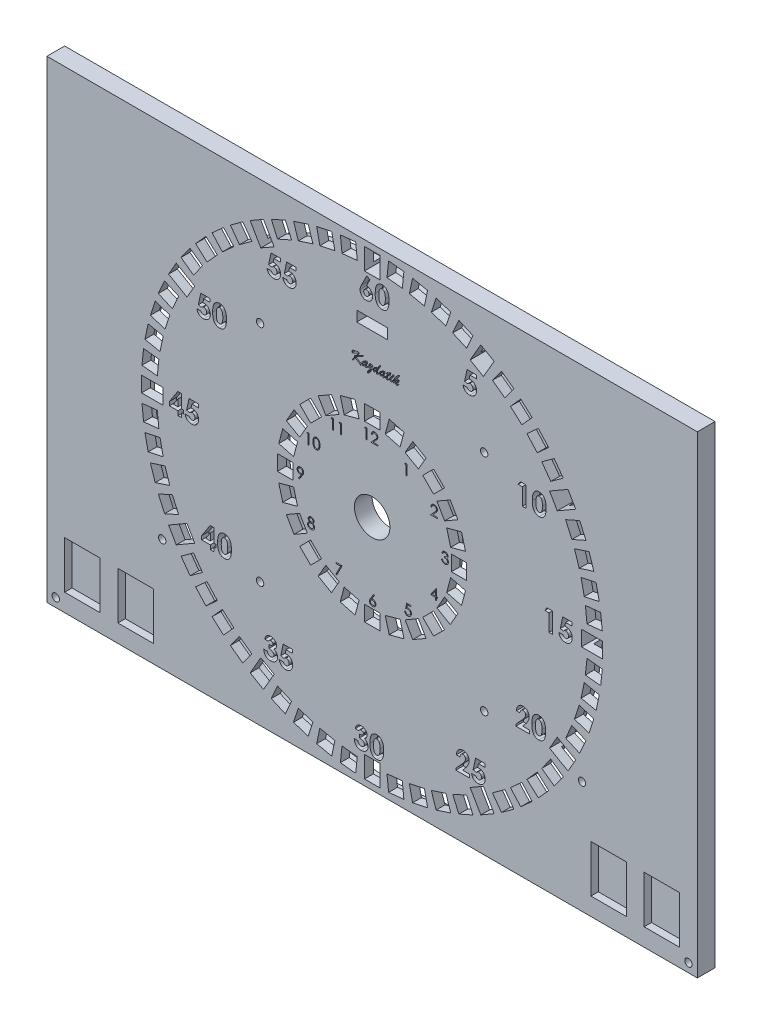
SolidWorks part; units mm, degrees
ref_plane "Front Plane" through (0, 0, 0) normal (0, 0, 1) x (1, 0, 0)
ref_plane "Top Plane" through (0, 0, 0) normal (0, 1, 0) x (1, 0, 0)
ref_plane "Right Plane" through (0, 0, 0) normal (1, 0, 0) x (0, 0, -1)
sketch "Sketch1" plane through (0, 0, 0) normal (0, 0, 1) x (1, 0, 0)
  line L1 (0, 0) -> (220, 0)
  line L2 (0, 0) -> (0, 160)
  line L3 (0, 160) -> (220, 160)
  line L4 (220, 0) -> (220, 160)
  line L5 (112.6, 158) -> (107.4, 158)
  line L6 (107.4, 158) -> (107.4, 152.8)
  line L7 (107.4, 152.8) -> (112.6, 152.8)
  line L8 (112.6, 158) -> (112.6, 152.8)
  line L9 (115.5675, 157.8445) -> (115.0239, 152.673)
  line L16 (120.739, 157.3009) -> (115.5675, 157.8445)
  line L19 (120.739, 157.3009) -> (120.1954, 152.1294)
  line L20 (115.0239, 152.673) -> (120.1954, 152.1294)
  line L27 (123.6739, 156.8361) -> (122.5928, 151.7497)
  line L30 (128.7603, 155.7549) -> (123.6739, 156.8361)
  line L31 (128.7603, 155.7549) -> (127.6792, 150.6686)
  line L37 (122.5928, 151.7497) -> (127.6792, 150.6686)
  line L42 (131.6306, 154.9859) -> (130.0237, 150.0404)
  line L46 (136.5761, 153.379) -> (131.6306, 154.9859)
  line L48 (136.5761, 153.379) -> (134.9692, 148.4335)
  line L55 (130.0237, 150.0404) -> (134.9692, 148.4335)
  line L58 (139.3502, 152.3141) -> (137.2352, 147.5636)
  line L64 (144.1007, 150.199) -> (139.3502, 152.3141)
  line L68 (144.1007, 150.199) -> (141.9856, 145.4486)
  line L72 (104.8, 138.0481) -> (115.2, 138.0481)
  line L73 (115.2, 138.0481) -> (115.2, 134.5481)
  line L74 (115.2, 134.5481) -> (104.8, 134.5481)
  line L75 (104.8, 138.0481) -> (104.8, 134.5481)
  line L76 (137.2352, 147.5636) -> (141.9856, 145.4486)
  line L81 (146.7483, 148.85) -> (144.1483, 144.3466)
  line L86 (151.2517, 146.25) -> (146.7483, 148.85)
  line L95 (151.2517, 146.25) -> (148.6517, 141.7466)
  line L534 (144.1483, 144.3466) -> (148.6517, 141.7466)
  line L535 (153.7438, 144.6316) -> (150.6873, 140.4247)
  line L536 (157.9507, 141.5751) -> (153.7438, 144.6316)
  line L537 (157.9507, 141.5751) -> (154.8942, 137.3682)
  line L538 (150.6873, 140.4247) -> (154.8942, 137.3682)
  line L539 (160.26, 139.705) -> (156.7805, 135.8407)
  line L540 (164.1244, 136.2256) -> (160.26, 139.705)
  line L541 (164.1244, 136.2256) -> (160.6449, 132.3612)
  line L542 (156.7805, 135.8407) -> (160.6449, 132.3612)
  line L543 (166.2256, 134.1244) -> (162.3612, 130.6449)
  line L544 (169.705, 130.26) -> (166.2256, 134.1244)
  line L545 (169.705, 130.26) -> (165.8407, 126.7805)
  line L546 (162.3612, 130.6449) -> (165.8407, 126.7805)
  line L547 (171.5751, 127.9507) -> (167.3682, 124.8942)
  line L548 (174.6316, 123.7438) -> (171.5751, 127.9507)
  line L549 (174.6316, 123.7438) -> (170.4247, 120.6873)
  line L550 (167.3682, 124.8942) -> (170.4247, 120.6873)
  line L551 (176.25, 121.2517) -> (171.7466, 118.6517)
  line L552 (178.85, 116.7483) -> (176.25, 121.2517)
  line L553 (178.85, 116.7483) -> (174.3466, 114.1483)
  line L554 (171.7466, 118.6517) -> (174.3466, 114.1483)
  line L555 (180.199, 114.1007) -> (175.4486, 111.9856)
  line L556 (182.3141, 109.3502) -> (180.199, 114.1007)
  line L557 (182.3141, 109.3502) -> (177.5636, 107.2352)
  line L558 (175.4486, 111.9856) -> (177.5636, 107.2352)
  line L559 (183.379, 106.5761) -> (178.4335, 104.9692)
  line L560 (184.9859, 101.6306) -> (183.379, 106.5761)
  line L561 (184.9859, 101.6306) -> (180.0404, 100.0237)
  line L562 (178.4335, 104.9692) -> (180.0404, 100.0237)
  line L563 (185.7549, 98.7603) -> (180.6686, 97.6792)
  line L564 (186.8361, 93.6739) -> (185.7549, 98.7603)
  line L565 (186.8361, 93.6739) -> (181.7497, 92.5928)
  line L566 (180.6686, 97.6792) -> (181.7497, 92.5928)
  line L567 (187.3009, 90.739) -> (182.1294, 90.1954)
  line L568 (187.8445, 85.5675) -> (187.3009, 90.739)
  line L569 (187.8445, 85.5675) -> (182.673, 85.0239)
  line L570 (182.1294, 90.1954) -> (182.673, 85.0239)
  line L571 (188, 82.6) -> (182.8, 82.6)
  line L572 (188, 77.4) -> (188, 82.6)
  line L573 (188, 77.4) -> (182.8, 77.4)
  line L574 (182.8, 82.6) -> (182.8, 77.4)
  line L575 (187.8445, 74.4325) -> (182.673, 74.9761)
  line L576 (187.3009, 69.261) -> (187.8445, 74.4325)
  line L577 (187.3009, 69.261) -> (182.1294, 69.8046)
  line L578 (182.673, 74.9761) -> (182.1294, 69.8046)
  line L579 (186.8361, 66.3261) -> (181.7497, 67.4072)
  line L580 (185.7549, 61.2397) -> (186.8361, 66.3261)
  line L581 (185.7549, 61.2397) -> (180.6686, 62.3208)
  line L582 (181.7497, 67.4072) -> (180.6686, 62.3208)
  line L583 (184.9859, 58.3694) -> (180.0404, 59.9763)
  line L584 (183.379, 53.4239) -> (184.9859, 58.3694)
  line L585 (183.379, 53.4239) -> (178.4335, 55.0308)
  line L586 (180.0404, 59.9763) -> (178.4335, 55.0308)
  line L587 (182.3141, 50.6498) -> (177.5636, 52.7648)
  line L588 (180.199, 45.8993) -> (182.3141, 50.6498)
  line L589 (180.199, 45.8993) -> (175.4486, 48.0144)
  line L590 (177.5636, 52.7648) -> (175.4486, 48.0144)
  line L591 (178.85, 43.2517) -> (174.3466, 45.8517)
  line L592 (176.25, 38.7483) -> (178.85, 43.2517)
  line L593 (176.25, 38.7483) -> (171.7466, 41.3483)
  line L594 (174.3466, 45.8517) -> (171.7466, 41.3483)
  line L595 (174.6316, 36.2562) -> (170.4247, 39.3127)
  line L596 (171.5751, 32.0493) -> (174.6316, 36.2562)
  line L597 (171.5751, 32.0493) -> (167.3682, 35.1058)
  line L598 (170.4247, 39.3127) -> (167.3682, 35.1058)
  line L599 (169.705, 29.74) -> (165.8407, 33.2195)
  line L600 (166.2256, 25.8756) -> (169.705, 29.74)
  line L601 (166.2256, 25.8756) -> (162.3612, 29.3551)
  line L602 (165.8407, 33.2195) -> (162.3612, 29.3551)
  line L603 (164.1244, 23.7744) -> (160.6449, 27.6388)
  line L604 (160.26, 20.295) -> (164.1244, 23.7744)
  line L605 (160.26, 20.295) -> (156.7805, 24.1593)
  line L606 (160.6449, 27.6388) -> (156.7805, 24.1593)
  line L607 (157.9507, 18.4249) -> (154.8942, 22.6318)
  line L608 (153.7438, 15.3684) -> (157.9507, 18.4249)
  line L609 (153.7438, 15.3684) -> (150.6873, 19.5753)
  line L610 (154.8942, 22.6318) -> (150.6873, 19.5753)
  line L611 (151.2517, 13.75) -> (148.6517, 18.2534)
  line L612 (146.7483, 11.15) -> (151.2517, 13.75)
  line L613 (146.7483, 11.15) -> (144.1483, 15.6534)
  line L614 (148.6517, 18.2534) -> (144.1483, 15.6534)
  line L615 (144.1007, 9.801) -> (141.9856, 14.5514)
  line L616 (139.3502, 7.6859) -> (144.1007, 9.801)
  line L617 (139.3502, 7.6859) -> (137.2352, 12.4364)
  line L618 (141.9856, 14.5514) -> (137.2352, 12.4364)
  line L619 (136.5761, 6.621) -> (134.9692, 11.5665)
  line L620 (131.6306, 5.0141) -> (136.5761, 6.621)
  line L621 (131.6306, 5.0141) -> (130.0237, 9.9596)
  line L622 (134.9692, 11.5665) -> (130.0237, 9.9596)
  line L623 (128.7603, 4.2451) -> (127.6792, 9.3314)
  line L624 (123.6739, 3.1639) -> (128.7603, 4.2451)
  line L625 (123.6739, 3.1639) -> (122.5928, 8.2503)
  line L626 (127.6792, 9.3314) -> (122.5928, 8.2503)
  line L627 (120.739, 2.6991) -> (120.1954, 7.8706)
  line L628 (115.5675, 2.1555) -> (120.739, 2.6991)
  line L629 (115.5675, 2.1555) -> (115.0239, 7.327)
  line L630 (120.1954, 7.8706) -> (115.0239, 7.327)
  line L631 (112.6, 2) -> (112.6, 7.2)
  line L632 (107.4, 2) -> (112.6, 2)
  line L633 (107.4, 2) -> (107.4, 7.2)
  line L634 (112.6, 7.2) -> (107.4, 7.2)
  line L635 (104.4325, 2.1555) -> (104.9761, 7.327)
  line L636 (99.261, 2.6991) -> (104.4325, 2.1555)
  line L637 (99.261, 2.6991) -> (99.8046, 7.8706)
  line L638 (104.9761, 7.327) -> (99.8046, 7.8706)
  line L639 (96.3261, 3.1639) -> (97.4072, 8.2503)
  line L640 (91.2397, 4.2451) -> (96.3261, 3.1639)
  line L641 (91.2397, 4.2451) -> (92.3208, 9.3314)
  line L642 (97.4072, 8.2503) -> (92.3208, 9.3314)
  line L643 (88.3694, 5.0141) -> (89.9763, 9.9596)
  line L644 (83.4239, 6.621) -> (88.3694, 5.0141)
  line L645 (83.4239, 6.621) -> (85.0308, 11.5665)
  line L646 (89.9763, 9.9596) -> (85.0308, 11.5665)
  line L647 (80.6498, 7.6859) -> (82.7648, 12.4364)
  line L648 (75.8993, 9.801) -> (80.6498, 7.6859)
  line L649 (75.8993, 9.801) -> (78.0144, 14.5514)
  line L650 (82.7648, 12.4364) -> (78.0144, 14.5514)
  line L651 (73.2517, 11.15) -> (75.8517, 15.6534)
  line L652 (68.7483, 13.75) -> (73.2517, 11.15)
  line L653 (68.7483, 13.75) -> (71.3483, 18.2534)
  line L654 (75.8517, 15.6534) -> (71.3483, 18.2534)
  line L655 (66.2562, 15.3684) -> (69.3127, 19.5753)
  line L656 (62.0493, 18.4249) -> (66.2562, 15.3684)
  line L657 (62.0493, 18.4249) -> (65.1058, 22.6318)
  line L658 (69.3127, 19.5753) -> (65.1058, 22.6318)
  line L659 (59.74, 20.295) -> (63.2195, 24.1593)
  line L660 (55.8756, 23.7744) -> (59.74, 20.295)
  line L661 (55.8756, 23.7744) -> (59.3551, 27.6388)
  line L662 (63.2195, 24.1593) -> (59.3551, 27.6388)
  line L663 (53.7744, 25.8756) -> (57.6388, 29.3551)
  line L664 (50.295, 29.74) -> (53.7744, 25.8756)
  line L665 (50.295, 29.74) -> (54.1593, 33.2195)
  line L666 (57.6388, 29.3551) -> (54.1593, 33.2195)
  line L667 (48.4249, 32.0493) -> (52.6318, 35.1058)
  line L668 (45.3684, 36.2562) -> (48.4249, 32.0493)
  line L669 (45.3684, 36.2562) -> (49.5753, 39.3127)
  line L670 (52.6318, 35.1058) -> (49.5753, 39.3127)
  line L671 (43.75, 38.7483) -> (48.2534, 41.3483)
  line L672 (41.15, 43.2517) -> (43.75, 38.7483)
  line L673 (41.15, 43.2517) -> (45.6534, 45.8517)
  line L674 (48.2534, 41.3483) -> (45.6534, 45.8517)
  line L675 (39.801, 45.8993) -> (44.5514, 48.0144)
  line L676 (37.6859, 50.6498) -> (39.801, 45.8993)
  line L677 (37.6859, 50.6498) -> (42.4364, 52.7648)
  line L678 (44.5514, 48.0144) -> (42.4364, 52.7648)
  line L679 (36.621, 53.4239) -> (41.5665, 55.0308)
  line L680 (35.0141, 58.3694) -> (36.621, 53.4239)
  line L681 (35.0141, 58.3694) -> (39.9596, 59.9763)
  line L682 (41.5665, 55.0308) -> (39.9596, 59.9763)
  line L683 (34.2451, 61.2397) -> (39.3314, 62.3208)
  line L684 (33.1639, 66.3261) -> (34.2451, 61.2397)
  line L685 (33.1639, 66.3261) -> (38.2503, 67.4072)
  line L686 (39.3314, 62.3208) -> (38.2503, 67.4072)
  line L687 (32.6991, 69.261) -> (37.8706, 69.8046)
  line L688 (32.1555, 74.4325) -> (32.6991, 69.261)
  line L689 (32.1555, 74.4325) -> (37.327, 74.9761)
  line L690 (37.8706, 69.8046) -> (37.327, 74.9761)
  line L691 (32, 77.4) -> (37.2, 77.4)
  line L692 (32, 82.6) -> (32, 77.4)
  line L693 (32, 82.6) -> (37.2, 82.6)
  line L694 (37.2, 77.4) -> (37.2, 82.6)
  line L695 (32.1555, 85.5675) -> (37.327, 85.0239)
  line L696 (32.6991, 90.739) -> (32.1555, 85.5675)
  line L697 (32.6991, 90.739) -> (37.8706, 90.1954)
  line L698 (37.327, 85.0239) -> (37.8706, 90.1954)
  line L699 (33.1639, 93.6739) -> (38.2503, 92.5928)
  line L700 (34.2451, 98.7603) -> (33.1639, 93.6739)
  line L701 (34.2451, 98.7603) -> (39.3314, 97.6792)
  line L702 (38.2503, 92.5928) -> (39.3314, 97.6792)
  line L703 (35.0141, 101.6306) -> (39.9596, 100.0237)
  line L704 (36.621, 106.5761) -> (35.0141, 101.6306)
  line L705 (36.621, 106.5761) -> (41.5665, 104.9692)
  line L706 (39.9596, 100.0237) -> (41.5665, 104.9692)
  line L707 (37.6859, 109.3502) -> (42.4364, 107.2352)
  line L708 (39.801, 114.1007) -> (37.6859, 109.3502)
  line L709 (39.801, 114.1007) -> (44.5514, 111.9856)
  line L710 (42.4364, 107.2352) -> (44.5514, 111.9856)
  line L711 (41.15, 116.7483) -> (45.6534, 114.1483)
  line L712 (43.75, 121.2517) -> (41.15, 116.7483)
  line L713 (43.75, 121.2517) -> (48.2534, 118.6517)
  line L714 (45.6534, 114.1483) -> (48.2534, 118.6517)
  line L715 (45.3684, 123.7438) -> (49.5753, 120.6873)
  line L716 (48.4249, 127.9507) -> (45.3684, 123.7438)
  line L717 (48.4249, 127.9507) -> (52.6318, 124.8942)
  line L718 (49.5753, 120.6873) -> (52.6318, 124.8942)
  line L719 (50.295, 130.26) -> (54.1593, 126.7805)
  line L720 (53.7744, 134.1244) -> (50.295, 130.26)
  line L721 (53.7744, 134.1244) -> (57.6388, 130.6449)
  line L722 (54.1593, 126.7805) -> (57.6388, 130.6449)
  line L723 (55.8756, 136.2256) -> (59.3551, 132.3612)
  line L724 (59.74, 139.705) -> (55.8756, 136.2256)
  line L725 (59.74, 139.705) -> (63.2195, 135.8407)
  line L726 (59.3551, 132.3612) -> (63.2195, 135.8407)
  line L727 (62.0493, 141.5751) -> (65.1058, 137.3682)
  line L728 (66.2562, 144.6316) -> (62.0493, 141.5751)
  line L729 (66.2562, 144.6316) -> (69.3127, 140.4247)
  line L730 (65.1058, 137.3682) -> (69.3127, 140.4247)
  line L731 (68.7483, 146.25) -> (71.3483, 141.7466)
  line L732 (73.2517, 148.85) -> (68.7483, 146.25)
  line L733 (73.2517, 148.85) -> (75.8517, 144.3466)
  line L734 (71.3483, 141.7466) -> (75.8517, 144.3466)
  line L735 (75.8993, 150.199) -> (78.0144, 145.4486)
  line L736 (80.6498, 152.3141) -> (75.8993, 150.199)
  line L737 (80.6498, 152.3141) -> (82.7648, 147.5636)
  line L738 (78.0144, 145.4486) -> (82.7648, 147.5636)
  line L739 (83.4239, 153.379) -> (85.0308, 148.4335)
  line L740 (88.3694, 154.9859) -> (83.4239, 153.379)
  line L741 (88.3694, 154.9859) -> (89.9763, 150.0404)
  line L742 (85.0308, 148.4335) -> (89.9763, 150.0404)
  line L743 (91.2397, 155.7549) -> (92.3208, 150.6686)
  line L744 (96.3261, 156.8361) -> (91.2397, 155.7549)
  line L745 (96.3261, 156.8361) -> (97.4072, 151.7497)
  line L746 (92.3208, 150.6686) -> (97.4072, 151.7497)
  line L747 (99.261, 157.3009) -> (99.8046, 152.1294)
  line L748 (104.4325, 157.8445) -> (99.261, 157.3009)
  line L749 (104.4325, 157.8445) -> (104.9761, 152.673)
  line L750 (99.8046, 152.1294) -> (104.9761, 152.673)
  line L751 (107.4, 152.8) -> (107.4, 150.8)
  line L752 (107.4, 152.8) -> (107.4, 150.8)
  line L753 (107.4, 150.8) -> (112.6, 150.8)
  line L754 (112.6, 150.8) -> (112.6, 152.8)
  line L755 (115.7708, 111.5826) -> (120.7936, 110.2367)
  line L756 (107.4, 112) -> (112.6, 112)
  line L757 (107.4, 112) -> (107.4, 106.8)
  line L758 (107.4, 106.8) -> (112.6, 106.8)
  line L759 (112.6, 112) -> (112.6, 106.8)
  line L760 (115.7708, 111.5826) -> (114.4249, 106.5597)
  line L761 (120.7936, 110.2367) -> (119.4478, 105.2139)
  line L762 (114.4249, 106.5597) -> (119.4478, 105.2139)
  line L763 (123.7483, 109.0128) -> (128.2517, 106.4128)
  line L764 (123.7483, 109.0128) -> (121.1483, 104.5095)
  line L765 (128.2517, 106.4128) -> (125.6517, 101.9095)
  line L766 (121.1483, 104.5095) -> (125.6517, 101.9095)
  line L767 (130.7889, 104.4659) -> (134.4659, 100.7889)
  line L768 (130.7889, 104.4659) -> (127.112, 100.7889)
  line L769 (134.4659, 100.7889) -> (130.7889, 97.112)
  line L770 (127.112, 100.7889) -> (130.7889, 97.112)
  line L771 (136.4128, 98.2517) -> (139.0128, 93.7483)
  line L772 (136.4128, 98.2517) -> (131.9095, 95.6517)
  line L773 (139.0128, 93.7483) -> (134.5095, 91.1483)
  line L774 (131.9095, 95.6517) -> (134.5095, 91.1483)
  line L775 (140.2367, 90.7936) -> (141.5826, 85.7708)
  line L776 (140.2367, 90.7936) -> (135.2139, 89.4478)
  line L777 (141.5826, 85.7708) -> (136.5597, 84.4249)
  line L778 (135.2139, 89.4478) -> (136.5597, 84.4249)
  line L779 (142, 82.6) -> (142, 77.4)
  line L780 (142, 82.6) -> (136.8, 82.6)
  line L781 (142, 77.4) -> (136.8, 77.4)
  line L782 (136.8, 82.6) -> (136.8, 77.4)
  line L783 (141.5826, 74.2292) -> (140.2367, 69.2064)
  line L784 (141.5826, 74.2292) -> (136.5597, 75.5751)
  line L785 (140.2367, 69.2064) -> (135.2139, 70.5522)
  line L786 (136.5597, 75.5751) -> (135.2139, 70.5522)
  line L787 (139.0128, 66.2517) -> (136.4128, 61.7483)
  line L788 (139.0128, 66.2517) -> (134.5095, 68.8517)
  line L789 (136.4128, 61.7483) -> (131.9095, 64.3483)
  line L790 (134.5095, 68.8517) -> (131.9095, 64.3483)
  line L791 (134.4659, 59.2111) -> (130.7889, 55.5341)
  line L792 (134.4659, 59.2111) -> (130.7889, 62.888)
  line L793 (130.7889, 55.5341) -> (127.112, 59.2111)
  line L794 (130.7889, 62.888) -> (127.112, 59.2111)
  line L795 (128.2517, 53.5872) -> (123.7483, 50.9872)
  line L796 (128.2517, 53.5872) -> (125.6517, 58.0905)
  line L797 (123.7483, 50.9872) -> (121.1483, 55.4905)
  line L798 (125.6517, 58.0905) -> (121.1483, 55.4905)
  line L799 (120.7936, 49.7633) -> (115.7708, 48.4174)
  line L800 (120.7936, 49.7633) -> (119.4478, 54.7861)
  line L801 (115.7708, 48.4174) -> (114.4249, 53.4403)
  line L802 (119.4478, 54.7861) -> (114.4249, 53.4403)
  line L803 (112.6, 48) -> (107.4, 48)
  line L804 (112.6, 48) -> (112.6, 53.2)
  line L805 (107.4, 48) -> (107.4, 53.2)
  line L806 (112.6, 53.2) -> (107.4, 53.2)
  line L807 (104.2292, 48.4174) -> (99.2064, 49.7633)
  line L808 (104.2292, 48.4174) -> (105.5751, 53.4403)
  line L809 (99.2064, 49.7633) -> (100.5522, 54.7861)
  line L810 (105.5751, 53.4403) -> (100.5522, 54.7861)
  line L811 (96.2517, 50.9872) -> (91.7483, 53.5872)
  line L812 (96.2517, 50.9872) -> (98.8517, 55.4905)
  line L813 (91.7483, 53.5872) -> (94.3483, 58.0905)
  line L814 (98.8517, 55.4905) -> (94.3483, 58.0905)
  line L815 (89.2111, 55.5341) -> (85.5341, 59.2111)
  line L816 (89.2111, 55.5341) -> (92.888, 59.2111)
  line L817 (85.5341, 59.2111) -> (89.2111, 62.888)
  line L818 (92.888, 59.2111) -> (89.2111, 62.888)
  line L819 (83.5872, 61.7483) -> (80.9872, 66.2517)
  line L820 (83.5872, 61.7483) -> (88.0905, 64.3483)
  line L821 (80.9872, 66.2517) -> (85.4905, 68.8517)
  line L822 (88.0905, 64.3483) -> (85.4905, 68.8517)
  line L823 (79.7633, 69.2064) -> (78.4174, 74.2292)
  line L824 (79.7633, 69.2064) -> (84.7861, 70.5522)
  line L825 (78.4174, 74.2292) -> (83.4403, 75.5751)
  line L826 (84.7861, 70.5522) -> (83.4403, 75.5751)
  line L827 (78, 77.4) -> (78, 82.6)
  line L828 (78, 77.4) -> (83.2, 77.4)
  line L829 (78, 82.6) -> (83.2, 82.6)
  line L830 (83.2, 77.4) -> (83.2, 82.6)
  line L831 (78.4174, 85.7708) -> (79.7633, 90.7936)
  line L832 (78.4174, 85.7708) -> (83.4403, 84.4249)
  line L833 (79.7633, 90.7936) -> (84.7861, 89.4478)
  line L834 (83.4403, 84.4249) -> (84.7861, 89.4478)
  line L835 (80.9872, 93.7483) -> (83.5872, 98.2517)
  line L836 (80.9872, 93.7483) -> (85.4905, 91.1483)
  line L837 (83.5872, 98.2517) -> (88.0905, 95.6517)
  line L838 (85.4905, 91.1483) -> (88.0905, 95.6517)
  line L839 (85.5341, 100.7889) -> (89.2111, 104.4659)
  line L840 (85.5341, 100.7889) -> (89.2111, 97.112)
  line L841 (89.2111, 104.4659) -> (92.888, 100.7889)
  line L842 (89.2111, 97.112) -> (92.888, 100.7889)
  line L843 (91.7483, 106.4128) -> (96.2517, 109.0128)
  line L844 (91.7483, 106.4128) -> (94.3483, 101.9095)
  line L845 (96.2517, 109.0128) -> (98.8517, 104.5095)
  line L846 (94.3483, 101.9095) -> (98.8517, 104.5095)
  line L847 (99.2064, 110.2367) -> (104.2292, 111.5826)
  line L848 (99.2064, 110.2367) -> (100.5522, 105.2139)
  line L849 (104.2292, 111.5826) -> (105.5751, 106.5597)
  line L850 (100.5522, 105.2139) -> (105.5751, 106.5597)
  line L851 (143.1483, 142.6146) -> (147.6517, 140.0146)
  line L852 (147.6517, 140.0146) -> (148.6517, 141.7466)
  line L853 (144.1483, 144.3466) -> (148.6517, 141.7466)
  line L854 (144.1483, 144.3466) -> (143.1483, 142.6146)
  line L855 (170.0146, 117.6517) -> (172.6146, 113.1483)
  line L856 (172.6146, 113.1483) -> (174.3466, 114.1483)
  line L857 (171.7466, 118.6517) -> (174.3466, 114.1483)
  line L858 (171.7466, 118.6517) -> (170.0146, 117.6517)
  line L859 (180.8, 82.6) -> (180.8, 77.4)
  line L860 (180.8, 77.4) -> (182.8, 77.4)
  line L861 (182.8, 82.6) -> (182.8, 77.4)
  line L862 (182.8, 82.6) -> (180.8, 82.6)
  line L863 (172.6146, 46.8517) -> (170.0146, 42.3483)
  line L864 (170.0146, 42.3483) -> (171.7466, 41.3483)
  line L865 (174.3466, 45.8517) -> (171.7466, 41.3483)
  line L866 (174.3466, 45.8517) -> (172.6146, 46.8517)
  line L867 (147.6517, 19.9854) -> (143.1483, 17.3854)
  line L868 (143.1483, 17.3854) -> (144.1483, 15.6534)
  line L869 (148.6517, 18.2534) -> (144.1483, 15.6534)
  line L870 (148.6517, 18.2534) -> (147.6517, 19.9854)
  line L871 (112.6, 9.2) -> (107.4, 9.2)
  line L872 (107.4, 9.2) -> (107.4, 7.2)
  line L873 (112.6, 7.2) -> (107.4, 7.2)
  line L874 (112.6, 7.2) -> (112.6, 9.2)
  line L875 (76.8517, 17.3854) -> (72.3483, 19.9854)
  line L876 (72.3483, 19.9854) -> (71.3483, 18.2534)
  line L877 (75.8517, 15.6534) -> (71.3483, 18.2534)
  line L878 (75.8517, 15.6534) -> (76.8517, 17.3854)
  line L879 (49.9854, 42.3483) -> (47.3854, 46.8517)
  line L880 (47.3854, 46.8517) -> (45.6534, 45.8517)
  line L881 (48.2534, 41.3483) -> (45.6534, 45.8517)
  line L882 (48.2534, 41.3483) -> (49.9854, 42.3483)
  line L883 (39.2, 77.4) -> (39.2, 82.6)
  line L884 (39.2, 82.6) -> (37.2, 82.6)
  line L885 (37.2, 77.4) -> (37.2, 82.6)
  line L886 (37.2, 77.4) -> (39.2, 77.4)
  line L887 (47.3854, 113.1483) -> (49.9854, 117.6517)
  line L888 (49.9854, 117.6517) -> (48.2534, 118.6517)
  line L889 (45.6534, 114.1483) -> (48.2534, 118.6517)
  line L890 (45.6534, 114.1483) -> (47.3854, 113.1483)
  line L891 (72.3483, 140.0146) -> (76.8517, 142.6146)
  line L892 (76.8517, 142.6146) -> (75.8517, 144.3466)
  line L893 (71.3483, 141.7466) -> (75.8517, 144.3466)
  line L894 (71.3483, 141.7466) -> (72.3483, 140.0146)
  line L895 (77, 80) -> (110, 80) construction
  circle A0 centre (110, 80) radius 6
  circle A1 centre (110, 80) radius 33
  circle A2 centre (110, 80) radius 80
  point P2 (110, 0)
  point P6 (110, 80)
  point P11 (143, 80)
  point P13 (110, 106.8)
  point P14 (110, 160)
  point P21 (110, 0)
  point P22 (190, 80)
  point P103 (110, 138.0481)
  point P109 (110, 134.5481)
  point P110 (110, 138.0481)
  point P267 (110, 80)
  point P268 (110, 113)
  point P271 (110, 112)
  point P273 (125.6517, 101.9095)
  point P274 (0, 0)
  point P367 (118.0623, 46.8651)
  point P412 (110, 80)
  point P413 (0, 0)
  point P414 (142, 80)
  point P415 (110, 48)
  point P416 (110, 47)
  point P417 (78, 80)
  dimension "D5" = 12
  dimension "D1" = 160
  dimension "D2" = 220
  dimension "D3" = 80
  dimension "D4" = 110
  dimension "D6" = 33
  dimension "D7" = 5.2
  dimension "D8" = 5.2
  dimension "D9" = 2
  dimension "D10" = 5.2
  dimension "D11" = 2.6
  dimension "D12" = 60
  dimension "D13" = 2
  dimension "D14" = 2
  dimension "D15" = 2
  dimension "D16" = 10.4
  dimension "D17" = 3.5
  dimension "D18" = 21.9519
  dimension "D19" = 1
  dimension "D20" = 5.2
  dimension "D21" = 5.2
  dimension "D22" = 24
  dimension "D23" = 1
  dimension "D24" = 5.2
  dimension "D25" = 1
  dimension "D26" = 12
  dimension "D27" = 1.7321
  dimension "D28" = 7.2
extrude "Boss-Extrude4" add sketch "Sketch1" along normal blind 6 contours A2 L3 L2 L1 | A2 L1 L4 L3 | A2 A1 L794 L786 L778 L774 L770 L766 L762 | A1 A0 | A2 A1 L754 L753 L751 L6 L5 L8 L750 L747 L748 L749 L746 L743 L744 L745 L742 L739 L740 L741 L738 L735 L736 L737 L734 L731 L732 L733 L730 L727 L728 L729 L726 L723 L724 L725 L722 L719 L720 L721 region at (26.9637, 80, 0) region at (193.0363, 80, 0) region at (30.2263, 80, 0) region at (77.9334, 80, 0)
extrude "Boss-Extrude5" add sketch "Sketch1<6>" along normal blind 1 contours L6 L7 L5 | L547 L550 L549 L548 | L794 L793 L791 L792 | L790 L789 L787 L788 | L786 L785 L783 L784 | L782 L781 L779 L780 | L778 L777 L775 L776 | L774 L773 L771 L772 | L770 L769 L767 L768 | L766 L765 L763 L764 | L762 L761 L755 L760 | L610 L609 L608 L607 | L611 L614 L613 L612 | L603 L606 L605 L604 | L7 L8 L5 L6 | L850 L849 L847 L848 | L842 L841 L839 L840 | L837 L838 L836 L835 | L834 L833 L831 L832 | L846 L845 L843 L844 region at (110, 155.4, 0)
sketch "Sketch1<6>" plane through (0, 0, 0) normal (0, 0, 1) x (1, 0, 0) same geometry as "Sketch1"
sketch "Sketch3" plane through (0, 0, 0) normal (0, 0, -1) x (-1, 0, 0)
  line L0 (-220, 0) -> (-220, 160) construction
  line L1 (0, 160) -> (-220, 160) construction
  line L2 (0, 0) -> (-220, 0) construction
  line L3 (-214, 6) -> (-202, 6)
  line L4 (-214, 6) -> (-214, 22)
  line L5 (-214, 22) -> (-202, 22)
  line L6 (-202, 6) -> (-202, 22)
  line L7 (-83.2, 77.4) -> (-83.2, 82.6) construction
  line L8 (-110, 159.8) -> (-110, 0.2) construction
  line L9 (-196, 6) -> (-184, 6)
  line L10 (-196, 6) -> (-196, 22)
  line L11 (-196, 22) -> (-184, 22)
  line L12 (-184, 6) -> (-184, 22)
  line L13 (-24, 22) -> (-36, 22)
  line L14 (-36, 6) -> (-36, 22)
  line L15 (-24, 6) -> (-36, 6)
  line L16 (-24, 6) -> (-24, 22)
  line L17 (-6, 22) -> (-18, 22)
  line L18 (-18, 6) -> (-18, 22)
  line L19 (-6, 6) -> (-18, 6)
  line L20 (-6, 6) -> (-6, 22)
  circle A0 centre (-110, 80) radius 79.8
  circle A1 centre (-110, 80) radius 72
  circle A2 centre (-110, 80) radius 34
  circle A3 centre (-110, 80) radius 24.8
  point P4 (-110, 159.8)
  point P9 (-76, 80)
  point P11 (-85.2, 80)
  point P35 (-83.2, 80)
  dimension "D1" = 0.2
  dimension "D2" = 7.8
  dimension "D3" = 34
  dimension "D4" = 2
  dimension "D5" = 6
  dimension "D6" = 6
  dimension "D7" = 16
  dimension "D8" = 12
  dimension "D9" = 12
  dimension "D10" = 16
  dimension "D11" = 6
  dimension "D12" = 6
extrude "Cut-Extrude9" cut sketch "Sketch3" against normal blind 3 contours A2 A3 | L8 A0 A1 | A0 L8 A1 | L8 A2 A3 region at (54.8346, 135.1654, 0) region at (111.7844, 155.9, 0) region at (86.496, 103.504, 0) region at (110.7603, 109.4, 0)
extrude "Cut-Extrude12" cut sketch "Sketch3<10>" against normal blind 1.5 contours L3 L6 L5 L4 | L9 L12 L11 L10 | L15 L16 L13 L14 | L19 L20 L17 L18 region at (208, 14, 0) region at (190, 14, 0) region at (30, 14, 0) region at (12, 14, 0)
sketch "Sketch3<10>" plane through (0, 0, 0) normal (0, 0, -1) x (-1, 0, 0) same geometry as "Sketch3"
sketch "Sketch5" plane through (0, 0, 6) normal (0, 0, 1) x (1, 0, 0)
  line L14 (98.8517, 55.4905) -> (94.3483, 58.0905) construction
  line L22 (42.4364, 107.2352) -> (44.5514, 111.9856) construction
  line L29 (76.8517, 17.3854) -> (72.3483, 19.9854) construction
  line L34 (104.9761, 7.327) -> (99.8046, 7.8706) construction
  line L35 (160.6449, 27.6388) -> (156.7805, 24.1593) construction
  text T0 "12"
  text T1 "1"
  text T2 "2"
  text T3 "3"
  text T4 "4"
  text T5 "5"
  text T6 "6"
  text T7 "7"
  text T8 "8"
  text T9 "9"
  text T10 "10"
  text T11 "11"
  text T12 "<b>60</b>" font "Century Gothic" height in points 26
  text T13 "<b>5</b>\r\n" font "Century Gothic" height in points 26
  text T14 "<b>10</b>" font "Century Gothic" height in points 26
  text T15 "<b>15</b>" font "Century Gothic" height in points 26
  text T16 "<b>20</b>" font "Century Gothic" height in points 26
  text T17 "<b>25</b>" font "Century Gothic" height in points 26
  text T18 "<b>30</b>" font "Century Gothic" height in points 26
  text T19 "Kazdatik\r\n" font "Brush Script MT" height 3.5
  text T20 "<b>35</b>" font "Century Gothic" height in points 26
  text T21 "<b>40</b>" font "Century Gothic" height in points 26
  text T22 "<b>45</b>" font "Century Gothic" height in points 26
  text T23 "<b>55</b>" font "Century Gothic" height in points 26
  text T24 "<b>50</b>" font "Century Gothic" height in points 26
  dimension "D1" = 5.0657
  dimension "D4" = 5.8362
  dimension "D5" = 7.2817
  dimension "D6" = 6.7922
  dimension "D7" = 4.8851
  dimension "D8" = 10.2103
  dimension "D9" = 3.4862
  dimension "D10" = 17.0186
  dimension "D11" = 4.8851
  dimension "D12" = 2.0444
  dimension "D13" = 1.657
  dimension "D14" = 4.8469
  dimension "D15" = 0.8323
  dimension "D16" = 3.8134
  dimension "D17" = 0.6897
  dimension "D18" = 3.0127
  dimension "D19" = 1.8083
  dimension "D20" = 2.55
  dimension "D21" = 1.2619
  dimension "D22" = 10.4968
  dimension "D23" = 1.6688
  dimension "D24" = 5.2801
  dimension "D25" = 35.0779
  dimension "D26" = 29.8881
  dimension "D27" = 32.4324
  dimension "D28" = 3.0772
  dimension "D29" = 33.0547
  dimension "D30" = 23.0569
  dimension "D31" = 35.8985
  dimension "D32" = 30.6075
  dimension "D33" = 7.9885
  dimension "D34" = 2.1852
  dimension "D35" = 32.8483
  dimension "D36" = 33.5469
  dimension "D37" = 31.2097
  dimension "D38" = 6.217
  dimension "D39" = 11.2386
  dimension "D40" = 53.1506
  dimension "D41" = 8.127
  dimension "D42" = 13.0475
  dimension "D43" = 27.2593
  dimension "D44" = 6.3451
  dimension "D45" = 2.0331
  dimension "D46" = 1.146
  dimension "D47" = 2.5148
  dimension "D48" = 12.951
  dimension "D49" = 15.0477
  dimension "D50" = 16.8398
  dimension "D51" = 28.0716
  dimension "D52" = 5.1529
extrude "Cut-Extrude13" cut sketch "Sketch5" against normal blind 2.5
sketch "Sketch7" plane through (0, 0, 6) normal (0, 0, 1) x (1, 0, 0)
  line L0 (0, 0) -> (220, 0) construction
  line L1 (6, 6) -> (18, 6)
  line L2 (6, 6) -> (6, 22)
  line L3 (6, 22) -> (18, 22)
  line L4 (18, 6) -> (18, 22)
  line L5 (0, 0) -> (0, 160) construction
  line L6 (220, 0) -> (220, 160) construction
  line L7 (24, 6) -> (36, 6)
  line L8 (24, 6) -> (24, 22)
  line L9 (24, 22) -> (36, 22)
  line L10 (36, 6) -> (36, 22)
  line L11 (214, 6) -> (202, 6)
  line L12 (214, 6) -> (214, 22)
  line L13 (214, 22) -> (202, 22)
  line L14 (202, 6) -> (202, 22)
  line L16 (196, 6) -> (184, 6)
  line L17 (196, 6) -> (196, 22)
  line L18 (196, 22) -> (184, 22)
  line L19 (184, 6) -> (184, 22)
  dimension "D1" = 6
  dimension "D2" = 6
  dimension "D3" = 12
  dimension "D4" = 16
  dimension "D5" = 6
  dimension "D6" = 6
  dimension "D7" = 16
  dimension "D8" = 12
  dimension "D9" = 6
  dimension "D10" = 6
  dimension "D11" = 12
  dimension "D12" = 16
  dimension "D13" = 12
  dimension "D14" = 16
  dimension "D15" = 6
  dimension "D16" = 6
extrude "Cut-Extrude16" cut sketch "Sketch7" against normal blind 2.5
sketch "Sketch8" plane through (0, 0, 6) normal (0, 0, 1) x (1, 0, 0)
  line L0 (0, 0) -> (220, 0) construction
  line L1 (0, 0) -> (0, 160) construction
  line L3 (36, 6) -> (36, 22) construction
  line L5 (110, 160) -> (110, 0) construction
  line L6 (0, 160) -> (220, 160) construction
  line L7 (72.1, 117.9) -> (110, 117.9)
  line L8 (110, 117.9) -> (147.9, 117.9)
  line L9 (72.1, 80) -> (147.9, 80) construction
  circle A0 centre (3, 3) radius 1.25
  circle A2 centre (39, 38) radius 1.25
  circle A4 centre (217, 3) radius 1.25
  circle A6 centre (181, 38) radius 1.25
  circle A8 centre (72.1, 117.9) radius 1.25
  circle A9 centre (147.9, 117.9) radius 1.25
  circle A10 centre (147.9, 42.1) radius 1.25
  circle A11 centre (72.1, 42.1) radius 1.25
  point P8 (110, 117.9)
  point P9 (110, 80)
  point P16 (147.9, 80)
  point P17 (147.9, 117.9)
  point P30 (147.9, 42.1)
  point P31 (110, 42.1)
  point P32 (72.1, 42.1)
  point P33 (72.1, 80)
  point P34 (72.1, 117.9)
  dimension "D3" = 2.5
  dimension "D11" = 2.5
  dimension "D25" = 2.5
  dimension "D4" = 38
  dimension "D1" = 3
  dimension "D2" = 3
  dimension "D10" = 3
  dimension "D13" = 37.9
  dimension "D14" = 37.9
  dimension "D15" = 37.9
  dimension "D17" = 37.9
  dimension "D18" = 37.9
  dimension "D19" = 37.9
  dimension "D20" = 37.9
  dimension "D21" = 37.9
  dimension "D22" = 37.9
  dimension "D23" = 37.9
  dimension "D24" = 75.8
extrude "Cut-Extrude17" cut sketch "Sketch8" against normal blind 6 contours A0 | A2 | A6 | A4 | A10 | A11 | A8 | A9
